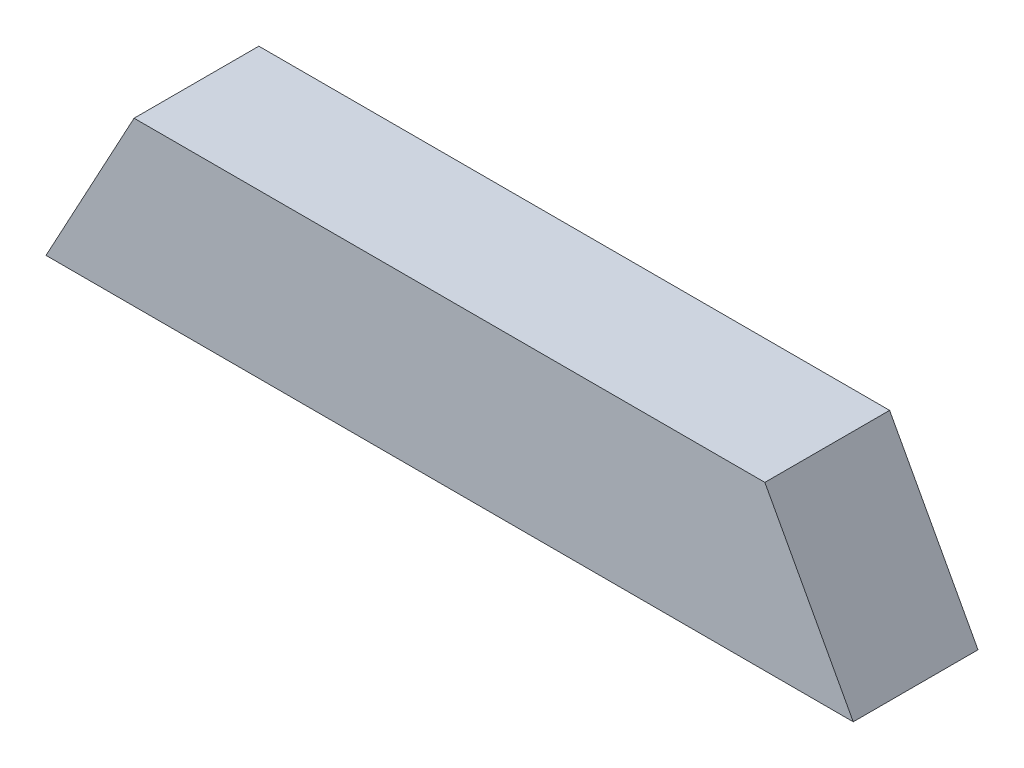
SolidWorks part; units mm, degrees
ref_plane "Front Plane" through (0, 0, 0) normal (0, 0, 1) x (1, 0, 0)
ref_plane "Top Plane" through (0, 0, 0) normal (0, 1, 0) x (1, 0, 0)
ref_plane "Right Plane" through (0, 0, 0) normal (1, 0, 0) x (0, 0, -1)
sketch "Sketch1" plane through (0, 0, 0) normal (0, 0, 1) x (1, 0, 0)
  line L4 (107.6489, 30.25) -> (-107.6846, 30.25)
  line L5 (-107.6846, 30.25) -> (-135.5119, -21.1986)
  line L6 (-132.2673, -15.1998) -> (132.3219, -15.3002)
  line L7 (135.5726, -21.3014) -> (107.6489, 30.25)
  line L8 (-142.3319, -21.196) -> (142.3976, -21.304)
  line L9 (142.3976, -21.304) -> (111.2226, 36.25)
  line L10 (111.2226, 36.25) -> (-111.2608, 36.25)
  line L11 (-111.2608, 36.25) -> (-142.3319, -21.196)
  line L12 (-107.6846, 30.25) -> (-132.2673, -15.1998) construction
  line L13 (132.3219, -15.3002) -> (107.6489, 30.25) construction
  dimension "D1" = 6
extrude "Boss-Extrude3" add sketch "Sketch1" along normal blind 38 contours L10 L11 L8 L5 L4 L7 L9 region at (-0.0179, 33.1549, 0)
extrude "Boss-Extrude4" add sketch "Sketch1<3>" against normal blind 6 contours L10 L11 L8 L5 L4 L7 L9 | L5 L8 L7 L6 | L6 L7 L4 L5 region at (0.0451, 6.7217, 0) region at (-0.0179, 33.1549, 0) region at (0.0288, -18.2621, 0)
sketch "Sketch1<3>" plane through (0, 0, 0) normal (0, 0, 1) x (1, 0, 0) same geometry as "Sketch1"
ref_plane "Plane1" through (0, 0, 16) normal (0, 0, -1) x (-1, 0, 0)
mirror "Mirror1" about plane through (0, 0, 16) normal (0, 0, -1) of "Boss-Extrude4"
